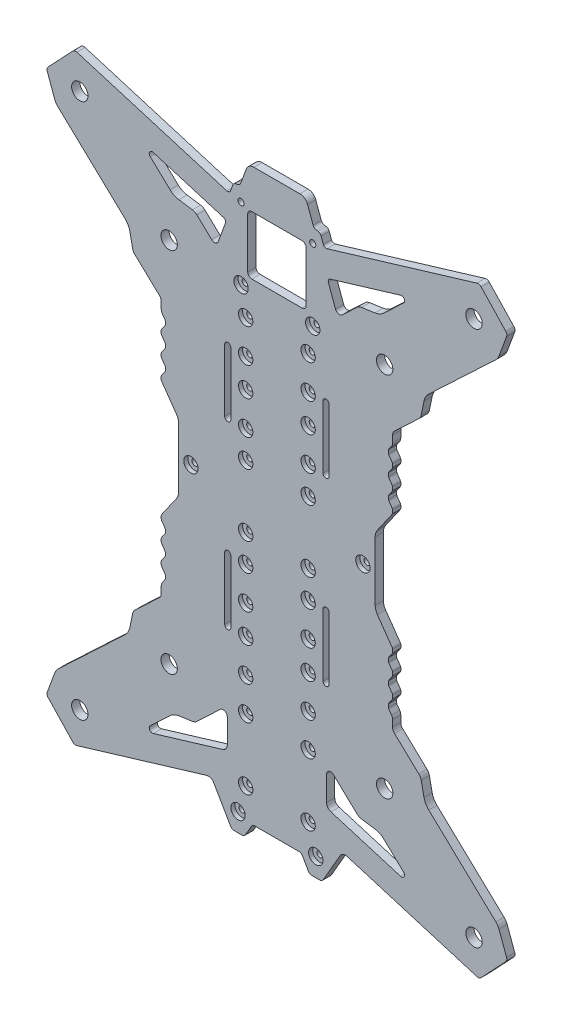
SolidWorks part; units mm, degrees
ref_plane "Front Plane" through (0, 0, 0) normal (0, 0, 1) x (1, 0, 0)
ref_plane "Top Plane" through (0, 0, 0) normal (0, 1, 0) x (1, 0, 0)
ref_plane "Right Plane" through (0, 0, 0) normal (1, 0, 0) x (0, 0, -1)
sketch "Model" plane through (0, 0, 0) normal (0, 0, 1) x (1, 0, 0)
  line L0 (183.8108, 197.417) -> (183.8108, 227.917)
  line L1 (186.8108, 227.917) -> (186.8108, 197.417)
  line L2 (138.8108, 139.917) -> (138.8108, 109.417)
  line L3 (135.8108, 109.417) -> (135.8108, 139.917)
  line L4 (186.8108, 139.917) -> (186.8108, 109.417)
  line L5 (183.8108, 109.417) -> (183.8108, 139.917)
  line L6 (135.8108, 197.417) -> (135.8108, 227.917)
  line L7 (138.8108, 227.917) -> (138.8108, 197.417)
  line L8 (147.0608, 264.0945) -> (147.0608, 288.5945)
  line L9 (173.5608, 262.0945) -> (149.0608, 262.0945)
  line L10 (175.5608, 288.5945) -> (175.5608, 264.0945)
  line L11 (149.0608, 290.5945) -> (173.5608, 290.5945)
  line L12 (133.6884, 72.3677) -> (122.1935, 61.5247)
  line L13 (120.0282, 60.4766) -> (113.4215, 59.5095)
  line L14 (100.8847, 45.7661) -> (134.926, 56.02)
  line L15 (209.2, 59.5095) -> (202.5933, 60.4766)
  line L16 (200.428, 61.5247) -> (188.9331, 72.3677)
  line L17 (185.5608, 58.8925) -> (185.5608, 70.9128)
  line L18 (187.6955, 56.02) -> (221.7368, 45.7661)
  line L19 (223.1987, 48.2935) -> (213.5306, 57.4133)
  line L20 (113.4215, 277.8244) -> (120.0282, 276.8573)
  line L21 (122.1935, 275.8092) -> (129.4288, 268.9842)
  line L22 (135.174, 281.2392) -> (100.8847, 291.5678)
  line L23 (99.4228, 289.0404) -> (109.0909, 279.9206)
  line L24 (261.0344, 314.783) -> (273.0616, 302.0327)
  line L25 (273.4849, 299.9728) -> (269.7846, 289.8648)
  line L26 (268.2674, 287.5628) -> (235.4884, 256.6428)
  line L27 (233.1432, 252.4417) -> (231.7925, 245.9027)
  line L28 (230.6199, 243.8022) -> (218.7522, 232.6075)
  line L29 (217.8108, 230.4252) -> (217.8108, 227.2161)
  line L30 (217.2682, 225.4954) -> (215.9916, 223.6722)
  line L31 (215.8108, 223.0986) -> (215.8108, 221.7292)
  line L32 (215.9916, 221.1557) -> (217.6299, 218.8159)
  line L33 (217.8108, 218.2423) -> (217.8108, 216.8729)
  line L34 (217.6299, 216.2994) -> (215.9916, 213.9596)
  line L35 (215.8108, 213.386) -> (215.8108, 212.0166)
  line L36 (215.9916, 211.4431) -> (217.6299, 209.1033)
  line L37 (217.8108, 208.5298) -> (217.8108, 207.1603)
  line L38 (217.6299, 206.5868) -> (215.9916, 204.247)
  line L39 (215.8108, 203.6735) -> (215.8108, 202.304)
  line L40 (215.9916, 201.7305) -> (217.6299, 199.3907)
  line L41 (217.8108, 198.8172) -> (217.8108, 197.4478)
  line L42 (217.6299, 196.8742) -> (210.3959, 186.5429)
  line L43 (209.3108, 183.1014) -> (209.3108, 154.2325)
  line L44 (210.3959, 150.791) -> (217.6299, 140.4597)
  line L45 (217.8108, 139.8861) -> (217.8108, 138.5167)
  line L46 (217.6299, 137.9432) -> (215.9916, 135.6034)
  line L47 (215.8108, 135.0299) -> (215.8108, 133.6605)
  line L48 (215.9916, 133.0869) -> (217.6299, 130.7471)
  line L49 (217.8108, 130.1736) -> (217.8108, 128.8042)
  line L50 (217.6299, 128.2306) -> (215.9916, 125.8908)
  line L51 (215.8108, 125.3173) -> (215.8108, 123.9479)
  line L52 (215.9916, 123.3743) -> (217.6299, 121.0345)
  line L53 (217.8108, 120.461) -> (217.8108, 119.0916)
  line L54 (217.6299, 118.518) -> (215.9916, 116.1782)
  line L55 (215.8108, 115.6047) -> (215.8108, 114.2353)
  line L56 (215.9916, 113.6617) -> (217.2682, 111.8385)
  line L57 (217.8108, 110.1178) -> (217.8108, 106.9087)
  line L58 (218.7522, 104.7264) -> (230.6199, 93.5317)
  line L59 (231.7925, 91.4312) -> (233.1432, 84.8922)
  line L60 (235.4884, 80.6911) -> (268.2674, 49.7711)
  line L61 (269.7846, 47.4691) -> (273.4849, 37.3611)
  line L62 (273.0616, 35.3012) -> (261.0344, 22.5509)
  line L63 (259.0027, 22.0083) -> (195.64, 41.0944)
  line L64 (192.1766, 39.7219) -> (183.942, 25.4591)
  line L65 (182.2099, 24.4591) -> (178.4116, 24.4591)
  line L66 (176.6796, 25.4591) -> (173.7928, 30.4591)
  line L67 (172.0608, 31.4591) -> (150.5608, 31.4591)
  line L68 (148.8287, 30.4591) -> (145.942, 25.4591)
  line L69 (144.2099, 24.4591) -> (140.4116, 24.4591)
  line L70 (138.6796, 25.4591) -> (130.4449, 39.7219)
  line L71 (126.9816, 41.0944) -> (63.6188, 22.0083)
  line L72 (61.5871, 22.5509) -> (49.5599, 35.3012)
  line L73 (49.1366, 37.3611) -> (52.8369, 47.4691)
  line L74 (54.3542, 49.7711) -> (87.1331, 80.6911)
  line L75 (89.4783, 84.8922) -> (90.8291, 91.4312)
  line L76 (92.0016, 93.5317) -> (103.8693, 104.7264)
  line L77 (104.8108, 106.9087) -> (104.8108, 110.1178)
  line L78 (105.3533, 111.8385) -> (106.6299, 113.6617)
  line L79 (106.8108, 114.2353) -> (106.8108, 115.6047)
  line L80 (106.6299, 116.1782) -> (104.9916, 118.518)
  line L81 (104.8108, 119.0916) -> (104.8108, 120.461)
  line L82 (104.9916, 121.0345) -> (106.6299, 123.3743)
  line L83 (106.6299, 125.8908) -> (104.9916, 128.2306)
  line L84 (104.8108, 128.8042) -> (104.8108, 130.1736)
  line L85 (104.9916, 130.7471) -> (106.6299, 133.0869)
  line L86 (106.8108, 133.6605) -> (106.8108, 135.0299)
  line L87 (106.6299, 135.6034) -> (104.9916, 137.9432)
  line L88 (104.8108, 138.5167) -> (104.8108, 139.8861)
  line L89 (104.9916, 140.4597) -> (112.2257, 150.791)
  line L90 (113.3108, 154.2325) -> (113.3108, 183.1014)
  line L91 (112.2257, 186.5429) -> (104.9916, 196.8742)
  line L92 (104.8108, 197.4478) -> (104.8108, 198.8172)
  line L93 (104.9916, 199.3907) -> (106.6299, 201.7305)
  line L94 (106.8108, 202.304) -> (106.8108, 203.6735)
  line L95 (106.6299, 204.247) -> (104.9916, 206.5868)
  line L96 (104.8108, 207.1603) -> (104.8108, 208.5298)
  line L97 (104.9916, 209.1033) -> (106.6299, 211.4431)
  line L98 (106.8108, 212.0166) -> (106.8108, 213.386)
  line L99 (106.6299, 213.9596) -> (104.9916, 216.2994)
  line L100 (104.8108, 216.8729) -> (104.8108, 218.2423)
  line L101 (104.9916, 218.8159) -> (106.6299, 221.1557)
  line L102 (106.8108, 221.7292) -> (106.8108, 223.0986)
  line L103 (106.6299, 223.6722) -> (105.3533, 225.4954)
  line L104 (104.8108, 227.2161) -> (104.8108, 230.4252)
  line L105 (103.8693, 232.6075) -> (92.0016, 243.8022)
  line L106 (90.8291, 245.9027) -> (89.4783, 252.4417)
  line L107 (87.1331, 256.6428) -> (54.3542, 287.5628)
  line L108 (52.8369, 289.8648) -> (49.1366, 299.9728)
  line L109 (49.5599, 302.0327) -> (61.5871, 314.783)
  line L110 (63.6188, 315.3256) -> (136.8099, 293.279)
  line L111 (138.6521, 294.2022) -> (139.728, 297.1583)
  line L112 (141.2601, 298.4439) -> (142.113, 298.5943)
  line L113 (143.6451, 299.8798) -> (146.325, 307.2429)
  line L114 (150.0838, 309.8748) -> (172.5378, 309.8748)
  line L115 (176.2965, 307.2429) -> (178.9765, 299.8798)
  line L116 (180.5086, 298.5943) -> (181.3614, 298.4439)
  line L117 (185.8116, 293.279) -> (259.0027, 315.3256)
  line L118 (193.1927, 268.9842) -> (200.428, 275.8092)
  line L119 (202.5933, 276.8573) -> (209.2, 277.8244)
  line L120 (221.7368, 291.5678) -> (187.4475, 281.2392)
  line L121 (186.4706, 279.2899) -> (189.941, 269.7551)
  line L122 (106.8108, 123.9479) -> (106.8108, 125.3173)
  line L123 (137.0608, 70.9128) -> (137.0608, 58.8925)
  line L124 (109.0909, 57.4133) -> (99.4228, 48.2935)
  line L125 (132.6805, 269.7551) -> (136.1509, 279.2899)
  line L126 (182.8935, 297.1583) -> (183.9694, 294.2022)
  line L127 (213.5306, 279.9206) -> (223.1987, 289.0404)
  circle A0 centre (178.8108, 292.022) radius 1.5
  arc A1 (183.8108, 197.417) -> (186.8108, 197.417) centre (185.3108, 197.417) ccw
  arc A2 (186.8108, 227.917) -> (183.8108, 227.917) centre (185.3108, 227.917) ccw
  arc A3 (138.8108, 139.917) -> (135.8108, 139.917) centre (137.3108, 139.917) ccw
  arc A4 (135.8108, 109.417) -> (138.8108, 109.417) centre (137.3108, 109.417) ccw
  circle A5 centre (213.9455, 258.3167) radius 4
  circle A6 centre (257.5914, 299.4875) radius 4
  circle A7 centre (65.0301, 299.4875) radius 4
  circle A8 centre (108.6761, 258.3167) radius 4
  circle A9 centre (108.6761, 79.0172) radius 4
  circle A10 centre (65.0301, 37.8464) radius 4
  circle A11 centre (257.5914, 37.8464) radius 4
  circle A12 centre (213.9455, 79.0172) radius 4
  arc A13 (186.8108, 139.917) -> (183.8108, 139.917) centre (185.3108, 139.917) ccw
  arc A14 (183.8108, 109.417) -> (186.8108, 109.417) centre (185.3108, 109.417) ccw
  arc A15 (135.8108, 197.417) -> (138.8108, 197.417) centre (137.3108, 197.417) ccw
  arc A16 (138.8108, 227.917) -> (135.8108, 227.917) centre (137.3108, 227.917) ccw
  circle A17 centre (143.8108, 292.022) radius 1.5
  arc A18 (147.0608, 264.0945) -> (149.0608, 262.0945) centre (149.0608, 264.0945) ccw
  arc A19 (173.5608, 262.0945) -> (175.5608, 264.0945) centre (173.5608, 264.0945) ccw
  arc A20 (175.5608, 288.5945) -> (173.5608, 290.5945) centre (173.5608, 288.5945) ccw
  arc A21 (149.0608, 290.5945) -> (147.0608, 288.5945) centre (149.0608, 288.5945) ccw
  circle A22 centre (146.0608, 227.917) radius 3.5 construction
  circle A23 centre (176.5608, 227.917) radius 3.5 construction
  circle A24 centre (176.5608, 197.417) radius 3.5 construction
  circle A25 centre (146.0608, 197.417) radius 3.5 construction
  circle A26 centre (119.3108, 168.667) radius 3.5 construction
  circle A27 centre (203.3108, 168.667) radius 3.5 construction
  circle A28 centre (146.0608, 183.917) radius 3.5 construction
  circle A29 centre (176.5608, 183.917) radius 3.5 construction
  circle A30 centre (146.0608, 153.417) radius 3.5 construction
  circle A31 centre (176.5608, 153.417) radius 3.5 construction
  circle A32 centre (146.0608, 139.917) radius 3.5 construction
  circle A33 centre (176.5608, 139.917) radius 3.5 construction
  circle A34 centre (146.0608, 109.417) radius 3.5 construction
  circle A35 centre (176.5608, 109.417) radius 3.5 construction
  circle A36 centre (146.0608, 76.667) radius 3.5 construction
  circle A37 centre (176.5608, 76.667) radius 3.5 construction
  circle A38 centre (146.0608, 46.167) radius 3.5 construction
  circle A39 centre (176.5608, 46.167) radius 3.5 construction
  circle A40 centre (142.3108, 33.4591) radius 3.5 construction
  circle A41 centre (180.3108, 33.4591) radius 3.5 construction
  circle A42 centre (176.5608, 93.042) radius 3.5 construction
  circle A43 centre (146.0608, 93.042) radius 3.5 construction
  circle A44 centre (176.5608, 123.542) radius 3.5 construction
  circle A45 centre (146.0608, 123.542) radius 3.5 construction
  circle A46 centre (176.5608, 213.792) radius 3.5 construction
  circle A47 centre (146.0608, 213.792) radius 3.5 construction
  circle A48 centre (176.5608, 244.292) radius 3.5 construction
  circle A49 centre (146.0608, 244.292) radius 3.5 construction
  circle A50 centre (178.8108, 257.022) radius 3.5 construction
  circle A51 centre (143.8108, 257.022) radius 3.5 construction
  arc A52 (137.0608, 70.9128) -> (133.6884, 72.3677) centre (135.0608, 70.9128) ccw
  arc A53 (120.0282, 60.4766) -> (122.1935, 61.5247) centre (119.4488, 64.4344) ccw
  arc A54 (113.4215, 59.5095) -> (109.0909, 57.4133) centre (114.5803, 51.5938) ccw
  arc A55 (99.4228, 48.2935) -> (100.8847, 45.7661) centre (100.4521, 47.2023) ccw
  arc A56 (134.926, 56.02) -> (137.0608, 58.8925) centre (134.0608, 58.8925) ccw
  arc A57 (200.428, 61.5247) -> (202.5933, 60.4766) centre (203.1727, 64.4344) ccw
  arc A58 (188.9331, 72.3677) -> (185.5608, 70.9128) centre (187.5608, 70.9128) ccw
  arc A59 (185.5608, 58.8925) -> (187.6955, 56.02) centre (188.5608, 58.8925) ccw
  arc A60 (221.7368, 45.7661) -> (223.1987, 48.2935) centre (222.1695, 47.2023) ccw
  arc A61 (213.5306, 57.4133) -> (209.2, 59.5095) centre (208.0412, 51.5938) ccw
  arc A62 (122.1935, 275.8092) -> (120.0282, 276.8573) centre (119.4488, 272.8995) ccw
  arc A63 (129.4288, 268.9842) -> (132.6805, 269.7551) centre (130.8012, 270.4391) ccw
  arc A64 (136.1509, 279.2899) -> (135.174, 281.2392) centre (134.7414, 279.8029) ccw
  arc A65 (100.8847, 291.5678) -> (99.4228, 289.0404) centre (100.4521, 290.1316) ccw
  arc A66 (109.0909, 279.9206) -> (113.4215, 277.8244) centre (114.5803, 285.7401) ccw
  arc A67 (261.0344, 314.783) -> (259.0027, 315.3256) centre (259.5795, 313.4106) ccw
  arc A68 (273.4849, 299.9728) -> (273.0616, 302.0327) centre (271.6068, 300.6603) ccw
  arc A69 (268.2674, 287.5628) -> (269.7846, 289.8648) centre (264.1503, 291.9274) ccw
  arc A70 (235.4884, 256.6428) -> (233.1432, 252.4417) centre (240.9778, 250.8233) ccw
  arc A71 (230.6199, 243.8022) -> (231.7925, 245.9027) centre (227.8752, 246.7119) ccw
  arc A72 (218.7522, 232.6075) -> (217.8108, 230.4252) centre (220.8108, 230.4252) ccw
  arc A73 (217.2682, 225.4954) -> (217.8108, 227.2161) centre (214.8108, 227.2161) ccw
  arc A74 (215.9916, 223.6722) -> (215.8108, 223.0986) centre (216.8108, 223.0986) ccw
  arc A75 (215.8108, 221.7292) -> (215.9916, 221.1557) centre (216.8108, 221.7292) ccw
  arc A76 (217.8108, 218.2423) -> (217.6299, 218.8159) centre (216.8108, 218.2423) ccw
  arc A77 (217.6299, 216.2994) -> (217.8108, 216.8729) centre (216.8108, 216.8729) ccw
  arc A78 (215.9916, 213.9596) -> (215.8108, 213.386) centre (216.8108, 213.386) ccw
  arc A79 (215.8108, 212.0166) -> (215.9916, 211.4431) centre (216.8108, 212.0166) ccw
  arc A80 (217.8108, 208.5298) -> (217.6299, 209.1033) centre (216.8108, 208.5298) ccw
  arc A81 (217.6299, 206.5868) -> (217.8108, 207.1603) centre (216.8108, 207.1603) ccw
  arc A82 (215.9916, 204.247) -> (215.8108, 203.6735) centre (216.8108, 203.6735) ccw
  arc A83 (215.8108, 202.304) -> (215.9916, 201.7305) centre (216.8108, 202.3041) ccw
  arc A84 (217.8108, 198.8172) -> (217.6299, 199.3907) centre (216.8108, 198.8172) ccw
  arc A85 (217.6299, 196.8742) -> (217.8108, 197.4478) centre (216.8108, 197.4478) ccw
  arc A86 (210.3959, 186.5429) -> (209.3108, 183.1014) centre (215.3108, 183.1014) ccw
  arc A87 (209.3108, 154.2325) -> (210.3959, 150.791) centre (215.3108, 154.2325) ccw
  arc A88 (217.8108, 139.8861) -> (217.6299, 140.4597) centre (216.8108, 139.8861) ccw
  arc A89 (217.6299, 137.9432) -> (217.8108, 138.5167) centre (216.8108, 138.5167) ccw
  arc A90 (215.9916, 135.6034) -> (215.8108, 135.0299) centre (216.8108, 135.0299) ccw
  arc A91 (215.8108, 133.6605) -> (215.9916, 133.0869) centre (216.8108, 133.6604) ccw
  arc A92 (217.8108, 130.1736) -> (217.6299, 130.7471) centre (216.8108, 130.1736) ccw
  arc A93 (217.6299, 128.2306) -> (217.8108, 128.8042) centre (216.8108, 128.8042) ccw
  arc A94 (215.9916, 125.8908) -> (215.8108, 125.3173) centre (216.8108, 125.3173) ccw
  arc A95 (215.8108, 123.9479) -> (215.9916, 123.3743) centre (216.8108, 123.9479) ccw
  arc A96 (217.8108, 120.461) -> (217.6299, 121.0345) centre (216.8108, 120.461) ccw
  arc A97 (217.6299, 118.518) -> (217.8108, 119.0916) centre (216.8108, 119.0916) ccw
  arc A98 (215.9916, 116.1782) -> (215.8108, 115.6047) centre (216.8108, 115.6047) ccw
  arc A99 (215.8108, 114.2353) -> (215.9916, 113.6617) centre (216.8108, 114.2353) ccw
  arc A100 (217.8108, 110.1178) -> (217.2682, 111.8385) centre (214.8108, 110.1178) ccw
  arc A101 (217.8108, 106.9087) -> (218.7522, 104.7264) centre (220.8108, 106.9087) ccw
  arc A102 (231.7925, 91.4312) -> (230.6199, 93.5317) centre (227.8752, 90.622) ccw
  arc A103 (233.1432, 84.8922) -> (235.4884, 80.6911) centre (240.9778, 86.5106) ccw
  arc A104 (269.7846, 47.4691) -> (268.2674, 49.7711) centre (264.1503, 45.4065) ccw
  arc A105 (273.0616, 35.3012) -> (273.4849, 37.3611) centre (271.6068, 36.6736) ccw
  arc A106 (259.0027, 22.0083) -> (261.0344, 22.5509) centre (259.5795, 23.9233) ccw
  arc A107 (195.64, 41.0944) -> (192.1766, 39.7219) centre (194.7747, 38.2219) ccw
  arc A108 (182.2099, 24.4591) -> (183.942, 25.4591) centre (182.2099, 26.4591) ccw
  arc A109 (176.6796, 25.4591) -> (178.4116, 24.4591) centre (178.4116, 26.4591) ccw
  arc A110 (173.7928, 30.4591) -> (172.0608, 31.4591) centre (172.0608, 29.4591) ccw
  arc A111 (150.5608, 31.4591) -> (148.8287, 30.4591) centre (150.5608, 29.4591) ccw
  arc A112 (144.2099, 24.4591) -> (145.942, 25.4591) centre (144.2099, 26.4591) ccw
  arc A113 (138.6796, 25.4591) -> (140.4116, 24.4591) centre (140.4116, 26.4591) ccw
  arc A114 (130.4449, 39.7219) -> (126.9816, 41.0944) centre (127.8468, 38.2219) ccw
  arc A115 (61.5871, 22.5509) -> (63.6188, 22.0083) centre (63.042, 23.9233) ccw
  arc A116 (49.1366, 37.3611) -> (49.5599, 35.3012) centre (51.0147, 36.6736) ccw
  arc A117 (54.3542, 49.7711) -> (52.8369, 47.4691) centre (58.4712, 45.4065) ccw
  arc A118 (87.1331, 80.6911) -> (89.4783, 84.8922) centre (81.6437, 86.5106) ccw
  arc A119 (92.0016, 93.5317) -> (90.8291, 91.4312) centre (94.7464, 90.622) ccw
  arc A120 (103.8693, 104.7264) -> (104.8108, 106.9087) centre (101.8108, 106.9087) ccw
  arc A121 (105.3533, 111.8385) -> (104.8108, 110.1178) centre (107.8108, 110.1178) ccw
  arc A122 (106.6299, 113.6617) -> (106.8108, 114.2353) centre (105.8108, 114.2353) ccw
  arc A123 (106.8108, 115.6047) -> (106.6299, 116.1782) centre (105.8108, 115.6047) ccw
  arc A124 (104.8108, 119.0916) -> (104.9916, 118.518) centre (105.8108, 119.0916) ccw
  arc A125 (104.9916, 121.0345) -> (104.8108, 120.461) centre (105.8108, 120.461) ccw
  arc A126 (106.6299, 123.3743) -> (106.8108, 123.9479) centre (105.8108, 123.9479) ccw
  arc A127 (106.8108, 125.3173) -> (106.6299, 125.8908) centre (105.8108, 125.3173) ccw
  arc A128 (104.8108, 128.8042) -> (104.9916, 128.2306) centre (105.8108, 128.8042) ccw
  arc A129 (104.9916, 130.7471) -> (104.8108, 130.1736) centre (105.8108, 130.1736) ccw
  arc A130 (106.6299, 133.0869) -> (106.8108, 133.6605) centre (105.8108, 133.6604) ccw
  arc A131 (106.8108, 135.0299) -> (106.6299, 135.6034) centre (105.8108, 135.0299) ccw
  arc A132 (104.8108, 138.5167) -> (104.9916, 137.9432) centre (105.8108, 138.5167) ccw
  arc A133 (104.9916, 140.4597) -> (104.8108, 139.8861) centre (105.8108, 139.8861) ccw
  arc A134 (112.2257, 150.791) -> (113.3108, 154.2325) centre (107.3108, 154.2325) ccw
  arc A135 (113.3108, 183.1014) -> (112.2257, 186.5429) centre (107.3108, 183.1014) ccw
  arc A136 (104.8108, 197.4478) -> (104.9916, 196.8742) centre (105.8108, 197.4478) ccw
  arc A137 (104.9916, 199.3907) -> (104.8108, 198.8172) centre (105.8108, 198.8172) ccw
  arc A138 (106.6299, 201.7305) -> (106.8108, 202.304) centre (105.8108, 202.3041) ccw
  arc A139 (106.8108, 203.6735) -> (106.6299, 204.247) centre (105.8108, 203.6735) ccw
  arc A140 (104.8108, 207.1603) -> (104.9916, 206.5868) centre (105.8108, 207.1603) ccw
  arc A141 (104.9916, 209.1033) -> (104.8108, 208.5298) centre (105.8108, 208.5298) ccw
  arc A142 (106.6299, 211.4431) -> (106.8108, 212.0166) centre (105.8108, 212.0166) ccw
  arc A143 (106.8108, 213.386) -> (106.6299, 213.9596) centre (105.8108, 213.386) ccw
  arc A144 (104.8108, 216.8729) -> (104.9916, 216.2994) centre (105.8108, 216.8729) ccw
  arc A145 (104.9916, 218.8159) -> (104.8108, 218.2423) centre (105.8108, 218.2423) ccw
  arc A146 (106.6299, 221.1557) -> (106.8108, 221.7292) centre (105.8108, 221.7292) ccw
  arc A147 (106.8108, 223.0986) -> (106.6299, 223.6722) centre (105.8108, 223.0986) ccw
  arc A148 (104.8108, 227.2161) -> (105.3533, 225.4954) centre (107.8108, 227.2161) ccw
  arc A149 (104.8108, 230.4252) -> (103.8693, 232.6075) centre (101.8108, 230.4252) ccw
  arc A150 (90.8291, 245.9027) -> (92.0016, 243.8022) centre (94.7464, 246.7119) ccw
  arc A151 (89.4783, 252.4417) -> (87.1331, 256.6428) centre (81.6437, 250.8233) ccw
  arc A152 (52.8369, 289.8648) -> (54.3542, 287.5628) centre (58.4712, 291.9274) ccw
  arc A153 (49.5599, 302.0327) -> (49.1366, 299.9728) centre (51.0147, 300.6603) ccw
  arc A154 (63.6188, 315.3256) -> (61.5871, 314.783) centre (63.042, 313.4106) ccw
  arc A155 (136.8099, 293.279) -> (138.6521, 294.2022) centre (137.2425, 294.7152) ccw
  arc A156 (141.2601, 298.4439) -> (139.728, 297.1583) centre (141.6074, 296.4743) ccw
  arc A157 (142.113, 298.5943) -> (143.6451, 299.8798) centre (141.7657, 300.5639) ccw
  arc A158 (150.0838, 309.8748) -> (146.325, 307.2429) centre (150.0838, 305.8748) ccw
  arc A159 (176.2965, 307.2429) -> (172.5378, 309.8748) centre (172.5378, 305.8748) ccw
  arc A160 (178.9765, 299.8798) -> (180.5086, 298.5943) centre (180.8559, 300.5639) ccw
  arc A161 (182.8935, 297.1583) -> (181.3614, 298.4439) centre (181.0141, 296.4743) ccw
  arc A162 (183.9694, 294.2022) -> (185.8116, 293.279) centre (185.379, 294.7152) ccw
  arc A163 (202.5933, 276.8573) -> (200.428, 275.8092) centre (203.1727, 272.8995) ccw
  arc A164 (209.2, 277.8244) -> (213.5306, 279.9206) centre (208.0412, 285.7401) ccw
  arc A165 (223.1987, 289.0404) -> (221.7368, 291.5678) centre (222.1695, 290.1316) ccw
  arc A166 (187.4475, 281.2392) -> (186.4706, 279.2899) centre (187.8801, 279.8029) ccw
  arc A167 (189.941, 269.7551) -> (193.1927, 268.9842) centre (191.8204, 270.4391) ccw
  circle A168 centre (176.5608, 227.917) radius 1.5
  circle A169 centre (146.0608, 227.917) radius 1.5
  circle A170 centre (146.0608, 123.542) radius 1.5
  circle A171 centre (176.5608, 123.542) radius 1.5
  circle A172 centre (146.0608, 93.042) radius 1.5
  circle A173 centre (176.5608, 93.042) radius 1.5
  circle A174 centre (180.3108, 33.4591) radius 1.5
  circle A175 centre (142.3108, 33.4591) radius 1.5
  circle A176 centre (176.5608, 76.667) radius 1.5
  circle A177 centre (146.0608, 76.667) radius 1.5
  circle A178 centre (146.0608, 109.417) radius 1.5
  circle A179 centre (119.3108, 168.667) radius 1.5
  circle A180 centre (176.5608, 139.917) radius 1.5
  circle A181 centre (146.0608, 139.917) radius 1.5
  circle A182 centre (146.0608, 213.792) radius 1.5
  circle A183 centre (176.5608, 213.792) radius 1.5
  circle A184 centre (176.5608, 109.417) radius 1.5
  circle A185 centre (176.5608, 197.417) radius 1.5
  circle A186 centre (176.5608, 244.292) radius 1.5
  circle A187 centre (203.3108, 168.667) radius 1.5
  circle A188 centre (143.8108, 257.022) radius 1.5
  circle A189 centre (178.8108, 257.022) radius 1.5
  circle A190 centre (146.0608, 244.292) radius 1.5
  circle A191 centre (146.0608, 46.167) radius 1.5
  circle A192 centre (146.0608, 197.417) radius 1.5
  circle A193 centre (176.5608, 46.167) radius 1.5
  circle A194 centre (146.0608, 183.917) radius 1.5
  circle A195 centre (146.0608, 153.417) radius 1.5
  circle A196 centre (176.5608, 153.417) radius 1.5
  circle A197 centre (176.5608, 183.917) radius 1.5
  point P570 (0, 0)
extrude "Boss-Extrude1" add sketch "Model" along normal blind 4
sketch "Sketch2" plane through (0, 0, 4) normal (0, 0, 1) x (1, 0, 0)
  circle A0 centre (176.5608, 46.167) radius 3.5 construction
  circle A1 centre (180.3108, 33.4591) radius 3.5 construction
  circle A2 centre (142.3108, 33.4591) radius 3.5 construction
  circle A3 centre (146.0608, 46.167) radius 3.5 construction
  circle A4 centre (176.5608, 76.667) radius 3.5 construction
  circle A5 centre (146.0608, 76.667) radius 3.5 construction
  circle A6 centre (146.0608, 93.042) radius 3.5 construction
  circle A7 centre (176.5608, 93.042) radius 3.5 construction
  circle A8 centre (176.5608, 109.417) radius 3.5 construction
  circle A9 centre (146.0608, 109.417) radius 3.5 construction
  circle A10 centre (176.5608, 123.542) radius 3.5 construction
  circle A11 centre (146.0608, 123.542) radius 3.5 construction
  circle A12 centre (146.0608, 139.917) radius 3.5 construction
  circle A13 centre (176.5608, 139.917) radius 3.5 construction
  circle A14 centre (176.5608, 139.917) radius 1.5 construction
  circle A15 centre (203.3108, 168.667) radius 3.5 construction
  circle A16 centre (176.5608, 153.417) radius 3.5 construction
  circle A17 centre (146.0608, 153.417) radius 3.5 construction
  circle A18 centre (119.3108, 168.667) radius 3.5 construction
  circle A19 centre (146.0608, 183.917) radius 3.5 construction
  circle A20 centre (176.5608, 183.917) radius 3.5 construction
  circle A21 centre (176.5608, 197.417) radius 3.5 construction
  circle A22 centre (146.0608, 197.417) radius 3.5 construction
  circle A23 centre (176.5608, 213.792) radius 3.5 construction
  circle A24 centre (146.0608, 213.792) radius 3.5 construction
  circle A25 centre (146.0608, 227.917) radius 3.5 construction
  circle A26 centre (176.5608, 227.917) radius 3.5 construction
  circle A27 centre (176.5608, 244.292) radius 3.5 construction
  circle A28 centre (178.8108, 257.022) radius 3.5 construction
  circle A29 centre (146.0608, 244.292) radius 3.5 construction
  circle A30 centre (143.8108, 257.022) radius 3.5 construction
  circle A31 centre (176.5608, 46.167) radius 3.5
  circle A32 centre (180.3108, 33.4591) radius 3.5
  circle A33 centre (142.3108, 33.4591) radius 3.5
  circle A34 centre (146.0608, 46.167) radius 3.5
  circle A35 centre (176.5608, 76.667) radius 3.5
  circle A36 centre (146.0608, 76.667) radius 3.5
  circle A37 centre (146.0608, 93.042) radius 3.5
  circle A38 centre (176.5608, 93.042) radius 3.5
  circle A39 centre (176.5608, 109.417) radius 3.5
  circle A40 centre (146.0608, 109.417) radius 3.5
  circle A41 centre (176.5608, 123.542) radius 3.5
  circle A42 centre (146.0608, 123.542) radius 3.5
  circle A43 centre (146.0608, 139.917) radius 3.5
  circle A44 centre (176.5608, 139.917) radius 3.5
  circle A45 centre (176.5608, 139.917) radius 1.5
  circle A46 centre (203.3108, 168.667) radius 3.5
  circle A47 centre (176.5608, 153.417) radius 3.5
  circle A48 centre (146.0608, 153.417) radius 3.5
  circle A49 centre (119.3108, 168.667) radius 3.5
  circle A50 centre (146.0608, 183.917) radius 3.5
  circle A51 centre (176.5608, 183.917) radius 3.5
  circle A52 centre (176.5608, 197.417) radius 3.5
  circle A53 centre (146.0608, 197.417) radius 3.5
  circle A54 centre (176.5608, 213.792) radius 3.5
  circle A55 centre (146.0608, 213.792) radius 3.5
  circle A56 centre (146.0608, 227.917) radius 3.5
  circle A57 centre (176.5608, 227.917) radius 3.5
  circle A58 centre (176.5608, 244.292) radius 3.5
  circle A59 centre (178.8108, 257.022) radius 3.5
  circle A60 centre (146.0608, 244.292) radius 3.5
  circle A61 centre (143.8108, 257.022) radius 3.5
extrude "Cut-Extrude1" cut sketch "Sketch2" against normal blind 2
